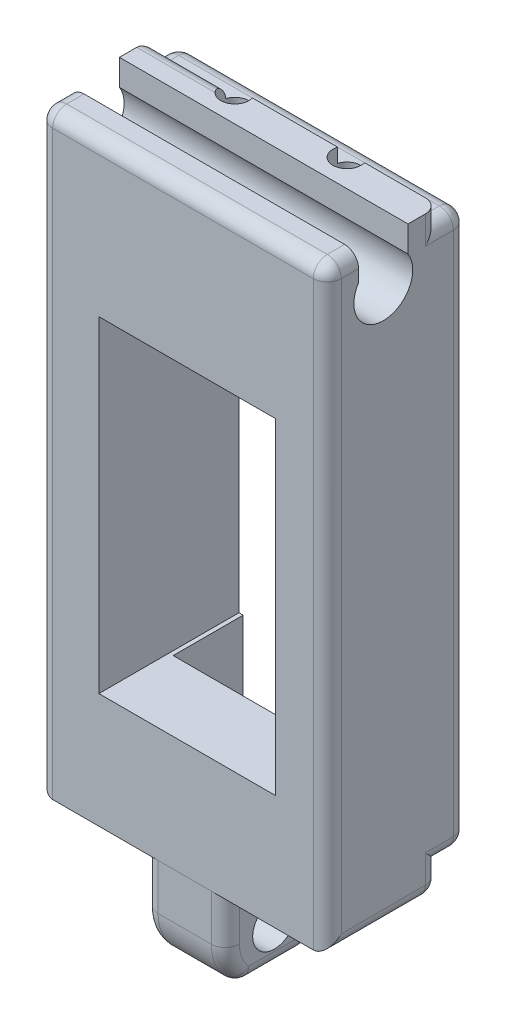
SolidWorks part; units mm, degrees
ref_plane "Front Plane" through (0, 0, 0) normal (0, 0, 1) x (1, 0, 0)
ref_plane "Top Plane" through (0, 0, 0) normal (0, 1, 0) x (1, 0, 0)
ref_plane "Right Plane" through (0, 0, 0) normal (1, 0, 0) x (0, 0, -1)
sketch "Sketch1" plane through (0, 0, 0) normal (0, 0, 1) x (1, 0, 0)
  line L0 (10.3, 0) -> (-10.3, 0)
  line L1 (0, 41.8397) -> (0, -28.0151) construction
  line L2 (-10.3, 0) -> (-10.3, 42.5)
  line L3 (-10.3, 42.5) -> (10.3, 42.5)
  line L4 (10.3, 42.5) -> (10.3, 0)
  point P6 (0, 0)
  dimension "D1" = 10.3
  dimension "D2" = 42.5
extrude "Boss-Extrude1" add sketch "Sketch1" along normal blind 10
sketch "Sketch11" plane through (0, 0, 0) normal (0, -1, 0) x (1, 0, 0)
  line L0 (-10.3, 10) -> (-10.3, 0) construction
  line L1 (-10.3, 0) -> (10.3, 0) construction
  line L4 (-10.3, 2.2959) -> (-10.3, 4.5918)
  line L5 (8.1, 2.2959) -> (-8.6978, 2.2959) construction
  line L6 (0, 0) -> (0, 6.168) construction
  circle A0 centre (4, 2.2959) radius 1
  circle A1 centre (-4, 2.2959) radius 1
  dimension "D2" = 2
  dimension "D1" = 4
  dimension "D3" = 2.2959
extrude "Cut-Extrude9" cut sketch "Sketch11" against normal up to surface (42.5 mm away) contours A0 | A1 up to face at (0, 42.5, 5)
sketch "Sketch13" plane through (0, 0, 0) normal (0, 0, -1) x (-1, 0, 0)
  line L0 (-10.3, 0) -> (-10.3, 42.5) construction
  line L1 (-10.3, 2) -> (10.3, 2)
  line L3 (-10.3, 41.5) -> (10.3, 41.5)
  line L5 (10.3, 42.5) -> (10.3, 0) construction
  line L7 (-10.3, 42.5) -> (10.3, 42.5)
  line L8 (-10.3, 42.5) -> (-10.3, 41.5)
  line L9 (-10.3, 41.5) -> (10.3, 41.5)
  line L10 (10.3, 42.5) -> (10.3, 41.5)
  line L11 (-10.3, 2) -> (10.3, 2)
  line L12 (-10.3, 2) -> (-10.3, 0)
  line L13 (-10.3, 0) -> (10.3, 0)
  line L14 (10.3, 2) -> (10.3, 0)
  line M5 (10.3, 0) -> (10.3, 42.5)
  line M6 (10.3, 42.5) -> (-10.3, 42.5)
  line M7 (-10.3, 42.5) -> (-10.3, 0)
  line M8 (-10.3, 0) -> (10.3, 0)
  dimension "D1" = 2
  dimension "D2" = 1
extrude "Cut-Extrude10" cut sketch "Sketch13" against normal blind 2 contours L3 M7 M5 M6 | L1 M7 M8 M5
ref_plane "Plane1" through (0, 0, 0) normal (-1, 0, 0) x (0, 0, 1)
sketch "Sketch14" plane through (0, 0, 0) normal (-1, 0, 0) x (0, 0, 1)
  line L0 (10, 42.5) -> (2, 42.5) construction
  line L1 (6, 27) -> (6, 30.6571) construction
  line L2 (7.7633, 42.5) -> (7.7633, 40.6406)
  line L3 (4.2367, 42.5) -> (7.7633, 42.5)
  line L4 (10, 42.5) -> (10, 0) construction
  line L6 (4.2367, 42.5) -> (4.2367, 40.6406)
  arc A0 (4.2367, 40.6406) -> (7.7633, 40.6406) centre (6, 39.5) ccw
  dimension "D1" = 4.2
  dimension "D2" = 4
  dimension "D3" = 3
extrude "Cut-Extrude16" cut sketch "Sketch14" against normal blind 14.1 and the other way blind 14.1
fillet "Fillet1" radius 1 16 edges at (10.3, 21.25, 10) (0, 42.5, 10) (-4.9552, 42, 2) (-10.3, 21.75, 0) (10.3, 42, 2) (-10.3, 42, 2) (0, 41.5, 0) (-10.3, 21.25, 10) (10.3, 21.75, 0) (10.3, 2, 1) (0, 2, 0) (-10.3, 1, 2) (-10.3, 2, 1) (10.3, 1, 2) (10.3, 0, 6) (-10.3, 0, 6)
sketch "Sketch15" plane through (0, 0, 0) normal (0, -1, 0) x (1, 0, 0)
  line L1 (3.0063, 9.9806) -> (-2.7937, 9.9806)
  line L2 (3.0063, 9.9806) -> (3.0063, 2.9806)
  line L3 (3.0063, 2.9806) -> (-2.7937, 2.9806)
  line L4 (-2.7937, 9.9806) -> (-2.7937, 2.9806)
  line L5 (3.0063, 9.9806) -> (-2.7937, 2.9806) construction
  line L6 (3.0063, 2.9806) -> (-2.7937, 9.9806) construction
  point P0 (0.1063, 6.4806)
  dimension "D1" = 7
  dimension "D2" = 5.8
extrude "Boss-Extrude2" add sketch "Sketch15" along normal blind 6
sketch "Sketch16" plane through (-2.7937, 0, 0) normal (-1, 0, 0) x (0, 0, 1)
  line L0 (9.9806, -6) -> (2.9806, -6) construction
  line L1 (9.9806, -6) -> (9.9806, 0) construction
  line L2 (2.9806, -3.3) -> (9.9806, -3.3)
  line L3 (2.9806, -3.3) -> (2.9806, -6.8086)
  line L4 (2.9806, -6.8086) -> (9.9806, -6.8086)
  line L5 (9.9806, -6.8086) -> (9.9806, -3.3)
  circle A0 centre (6.4806, -3.3) radius 1.55
  arc A1 (2.9806, -3.3) -> (9.9806, -3.3) centre (6.4806, -3.3) ccw
  line M3 (2.9806, 0) -> (2.9806, -6)
  line M4 (2.9806, -6) -> (9.9806, -6)
  line M5 (9.9806, -6) -> (9.9806, 0)
  dimension "D1" = 3.1
  dimension "D4" = 3.5
  dimension "D2" = 2.7
  dimension "D3" = 3.5
extrude "Cut-Extrude17" cut sketch "Sketch16" against normal blind 6 contours L2 A0 | L2 A0 | A1 M3 M4 | A1 M4 M5 | A1 L3 L4 L5 M4 | A1 M4
sketch "Sketch17" plane through (0, 0, 0) normal (0, 0, -1) x (-1, 0, 0)
  line L0 (-10.3, 3) -> (-10.3, 40.5) construction
  line L1 (-6.6, 31.5) -> (6, 31.5)
  line L2 (-6.6, 31.5) -> (-6.6, 8.2)
  line L3 (-6.6, 8.2) -> (6, 8.2)
  line L4 (6, 31.5) -> (6, 8.2)
  line L7 (10.3, 40.5) -> (9.3, 40.5) construction
  dimension "D1" = 12.6
  dimension "D2" = 3.7
  dimension "D3" = 23.3
  dimension "D4" = 9
extrude "Cut-Extrude18" cut sketch "Sketch17" against normal blind 10
fillet "Fillet5" radius 1 12 edges at (-2.7937, -1.65, 9.9806) (-2.7937, -6, 6.4806) (-2.7937, -1.65, 2.9806) (3.0063, -1.65, 2.9806) (3.0063, -6, 6.4806) (3.0063, -1.65, 9.9806) (-2.7937, -4.7925, 9.6464) (-2.7937, -4.7925, 3.3147) (3.0063, -4.7925, 3.3147) (3.0063, -4.7925, 9.6464) (0.1063, -6, 4.2535) (0.1063, -6, 8.7077)
sketch "Sketch18" plane through (0, 0, 0) normal (0, 0, -1) x (-1, 0, 0)
  line L0 (-6.6, 19.85) -> (14.3667, 19.85) construction
  line L1 (-6.6, 31.5) -> (-6.6, 8.2) construction
  line L2 (-0.3, 31.5) -> (-0.3, 5.7579) construction
  line L3 (6, 31.5) -> (-6.6, 31.5) construction
  line L4 (-6.3, 8.2) -> (5.7, 8.2)
  line L5 (-6.3, 31.5) -> (5.7, 31.5)
  line L6 (-6.3, 31.5) -> (-6.3, 37)
  line L7 (-6.3, 37) -> (5.7, 37)
  line L8 (5.7, 31.5) -> (5.7, 37)
  line L9 (5.7, 8.2) -> (5.7, 2.7)
  line L10 (-6.3, 2.7) -> (5.7, 2.7)
  line L11 (-6.3, 8.2) -> (-6.3, 2.7)
  dimension "D1" = 12
  dimension "D2" = 5.5
extrude "Cut-Extrude19" cut sketch "Sketch18" against normal blind 5
